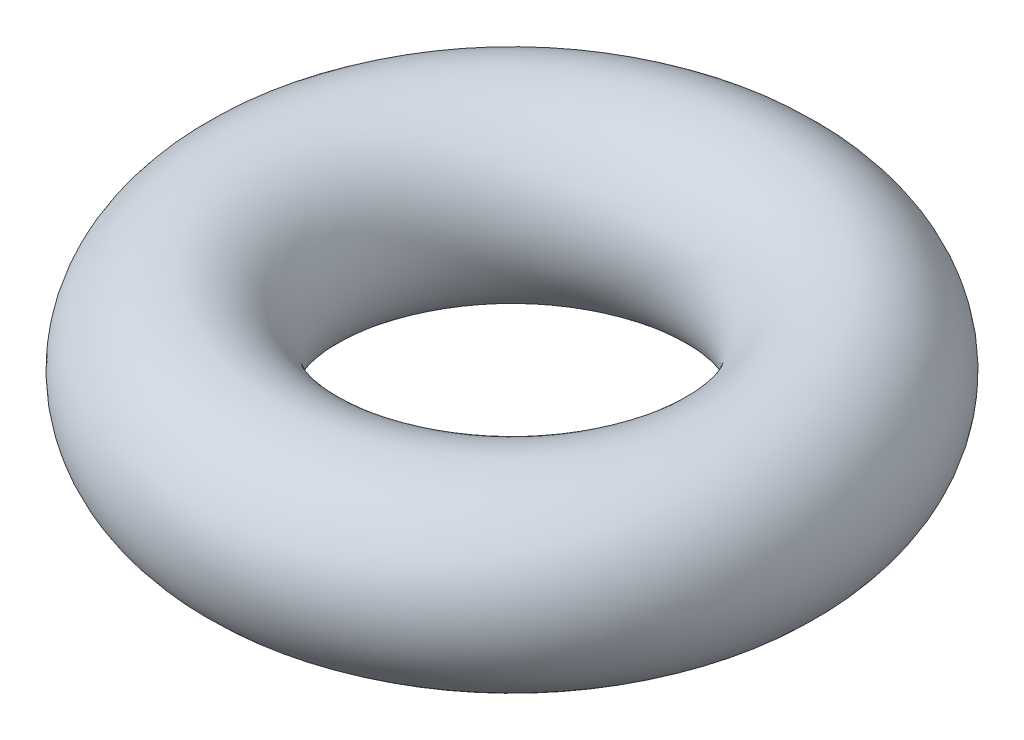
SolidWorks part; units mm, degrees
ref_plane "Front Plane" through (0, 0, 0) normal (0, 0, 1) x (1, 0, 0)
ref_plane "Top Plane" through (0, 0, 0) normal (0, 1, 0) x (1, 0, 0)
ref_plane "Right Plane" through (0, 0, 0) normal (1, 0, 0) x (0, 0, -1)
sketch "Sketch1" plane through (0, 0, 0) normal (0, 0, 1) x (1, 0, 0)
  line L0 (-1.4478, 0) -> (1.4478, 0) construction
  line L1 (-3.2258, 0) -> (3.2258, 0) construction
  circle A0 centre (-2.3368, 0) radius 0.889 construction
  dimension "Width" = 1.778
  dimension "ID" = 2.8956
  dimension "OD" = 6.4516
sketch "Sketch3" plane through (0, 0, 0) normal (1, 0, 0) x (0, 0, -1)
  line L0 (0, 0) -> (-0.9652, 0) construction
  line L1 (-0.9652, 0) -> (-0.9652, 0.889) construction
  point P0 (-0.9652, 0.889)
  dimension "D1" = 0.9652
  dimension "D2" = 0.889
sketch "Sketch2" plane through (0, 0, 0) normal (0, 0, 1) x (1, 0, 0)
  line L0 (0, 0) -> (0, 0.889) construction
  line L1 (-1.4478, 0) -> (1.4478, 0) construction
  circle A0 centre (-2.3368, 0) radius 0.889 construction
  circle A1 centre (-2.3368, 0) radius 0.889
  point P7 (-2.3368, 0.889)
revolve "Revolve1" add sketch "Sketch2" angle 360 about L0
ref_axis "Center Axis 1" through (0, 0.9779, 0) along (0, -1, 0)
sketch "Sketch4" plane through (0, 0, 0) normal (0, 1, 0) x (1, 0, 0)
  circle A0 centre (0, 0) radius 1.27
  dimension "D1" = 2.54
equation "\"D1@Sketch3\"=\"ID@Sketch1\"/3"
equation "\"D2@Sketch3\"=\"Width@Sketch1\"/2"
